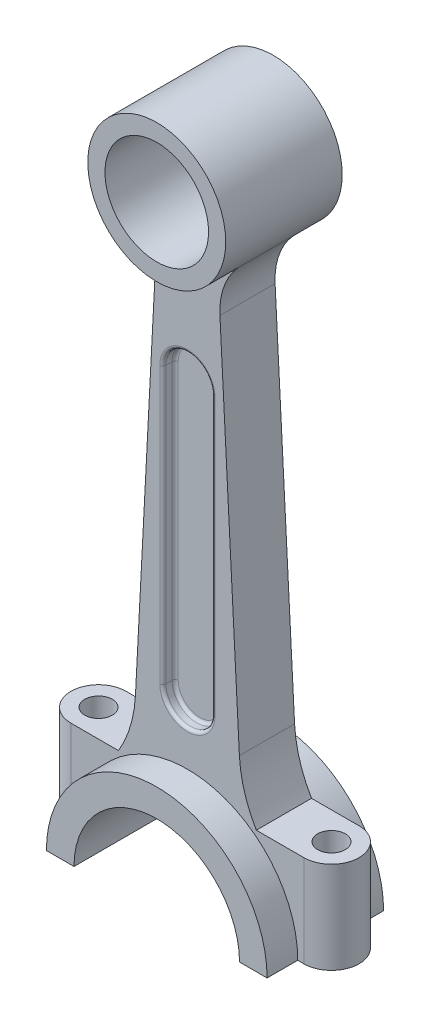
SolidWorks part; units mm, degrees
material "Pure Gold"
ref_plane "Front Plane" through (0, 0, 0) normal (0, 0, 1) x (1, 0, 0)
ref_plane "Top Plane" through (0, 0, 0) normal (0, 1, 0) x (1, 0, 0)
ref_plane "Right Plane" through (0, 0, 0) normal (1, 0, 0) x (0, 0, -1)
sketch "Sketch2" plane through (0, 0, 0) normal (0, 0, 1) x (1, 0, 0)
  line L0 (0, 100.6) -> (0, -100.6) construction
  line L1 (-17.8497, -69.3368) -> (-10, 80.4444)
  line L2 (17.8497, -69.3368) -> (10, 80.4444)
  line L3 (-36, -100.6) -> (-27, -100.6)
  line L4 (27, -100.6) -> (36, -100.6)
  circle A0 centre (0, 100.6) radius 16.9
  circle A1 centre (0, 100.6) radius 22.5
  arc A2 (36, -100.6) -> (-36, -100.6) centre (0, -100.6) ccw
  arc A3 (27, -100.6) -> (-27, -100.6) centre (0, -100.6) ccw
  point P6 (0, 0)
  dimension "D1" = 45
  dimension "D2" = 33.8
  dimension "D3" = 54
  dimension "D4" = 72
  dimension "D5" = 201.2
  dimension "D6" = 20
  dimension "D7" = 6
extrude "Boss-Extrude1" add sketch "Sketch2" along normal mid plane 38 contours A0 A1 | A2 A3 | L3 A3 L4 A2 region at (0, -65.405, 0) region at (-11.5231, 119.1805, 0)
extrude "Boss-Extrude2" add sketch "Sketch2<3>" along normal mid plane 18 contours A1 L0 A2 L2 | L0 A1 L1 A2 region at (7.1843, -0.2455, 0) region at (-7.1843, -0.2455, 0)
sketch "Sketch2<3>" plane through (0, 0, 0) normal (0, 0, 1) x (1, 0, 0) same geometry as "Sketch2"
sketch "Sketch3" plane through (0, 0, 9) normal (0, 0, 1) x (1, 0, 0)
  line L0 (0, 45) -> (0, -45) construction
  line L1 (8, 45) -> (8, -45)
  line L2 (-8, 45) -> (-8, -45)
  arc A0 (8, 45) -> (-8, 45) centre (0, 45) ccw
  arc A1 (-8, -45) -> (8, -45) centre (0, -45) ccw
  point P2 (0, 0)
  dimension "D2" = 8
  dimension "D1" = 90
extrude "Cut-Extrude1" cut sketch "Sketch3" against normal blind 4
mirror "Mirror2" about plane through (0, 0, 0) normal (0, 0, 1) of "Cut-Extrude1"
fillet "Fillet1" radius 1 16 edges at (0, 53, -9) (8, 0, -9) (0, -53, -9) (0, 53, 9) (8, 0, 9) (0, -53, 9) (-8, 0, -5) (0, -53, -5) (8, 0, -5) (0, 53, -5) (8, 0, 5) (0, -53, 5) (-8, 0, 5) (0, 53, 5) (-8, 0, -9) (-8, 0, 9)
fillet "Fillet2" radius 40 2 edges at (-17.8497, -69.3368, 0) (17.8497, -69.3368, 0)
fillet "Fillet3" radius 22.5 2 edges at (10, 80.4444, 0) (-10, 80.4444, 0)
ref_plane "Plane1" through (0, -70.6, 0) normal (0, -1, 0) x (-1, 0, 0)
sketch "Sketch5" plane through (0, -70.6, 0) normal (0, -1, 0) x (-1, 0, 0)
  line L0 (38, 0) -> (-38, 0) construction
  line L1 (38, -9) -> (-38, -9)
  line L2 (38, 9) -> (-38, 9)
  arc A0 (38, -9) -> (38, 9) centre (38, 0) ccw
  arc A1 (-38, 9) -> (-38, -9) centre (-38, 0) ccw
  point P2 (0, 0)
  dimension "D2" = 9
  dimension "D1" = 76
extrude "Boss-Extrude3" add sketch "Sketch5" along normal up to surface (30 mm away) up to face at (-31.5, -100.6, 0)
sketch "Sketch6" plane through (0, 0, -9) normal (0, 0, -1) x (-1, 0, 0)
  line L1 (-27, -100.6) -> (27, -100.6)
  line L2 (-27, -100.6) -> (27, -100.6)
  arc A1 (27, -100.6) -> (-27, -100.6) centre (0, -100.6) ccw
  arc A2 (27, -100.6) -> (-27, -100.6) centre (0, -100.6) ccw
  dimension "D1" = 0
extrude "Cut-Extrude2" cut sketch "Sketch6" against normal through all both and the other way through all
sketch "Sketch7" plane through (0, -70.6, 0) normal (0, 1, 0) x (1, 0, 0)
  circle A0 centre (38, 0) radius 4.5
  circle A1 centre (-38, 0) radius 4.5
  dimension "D1" = 9
  dimension "D2" = 9
extrude "Cut-Extrude3" cut sketch "Sketch7" against normal through all and the other way through all
